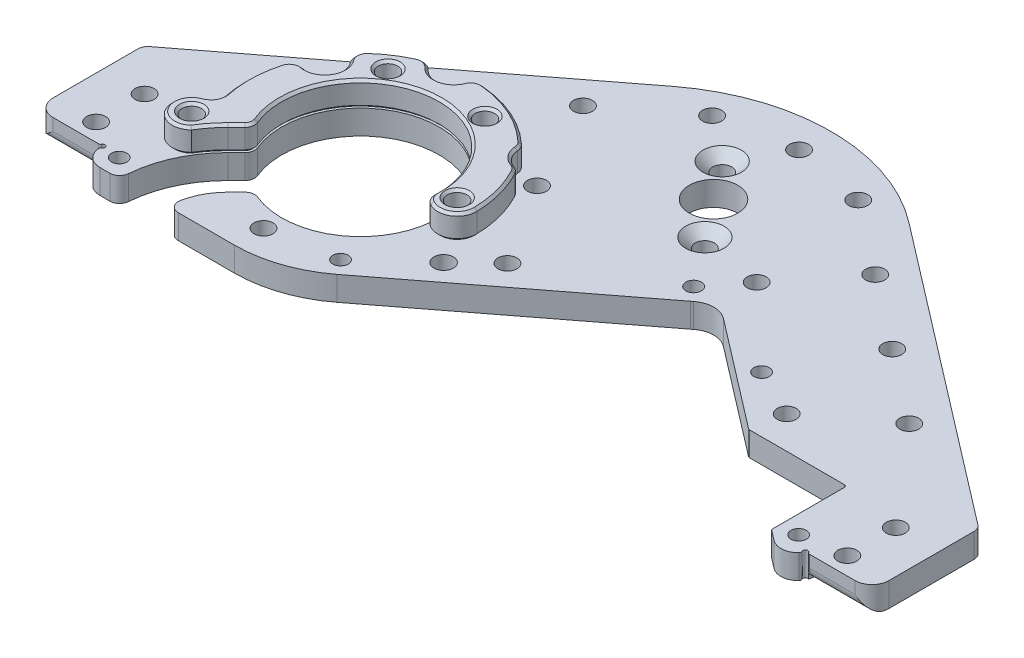
SolidWorks part; units mm, degrees
other "Weapon Motor Shock Spacer"
material "Alum Plate"
ref_plane "Front Plane" through (0, 0, 0) normal (0, 0, 1) x (1, 0, 0)
ref_plane "Top Plane" through (0, 0, 0) normal (0, 1, 0) x (1, 0, 0)
ref_plane "Right Plane" through (0, 0, 0) normal (1, 0, 0) x (0, 0, -1)
sketch "Top Layout" plane through (0, 0, 0) normal (0, 1, 0) x (1, 0, 0)
  line L0 (-114.046, -123.825) -> (-104.775, -123.825) construction
  line L1 (-104.775, -142.875) -> (-101.6, -142.875)
  line L2 (-104.775, -142.875) -> (-104.775, -104.775)
  line L3 (-104.775, -104.775) -> (-101.6, -104.775)
  line L4 (-101.6, -142.875) -> (-101.6, -104.775)
  line L5 (-104.775, -142.875) -> (-101.6, -104.775) construction
  line L6 (-104.775, -104.775) -> (-101.6, -142.875) construction
  line L7 (-19.05, -105.8164) -> (-101.6, -105.8164)
  line L8 (-19.05, -105.8164) -> (-19.05, -141.8336)
  line L9 (-19.05, -141.8336) -> (-101.6, -141.8336)
  line L10 (-101.6, -105.8164) -> (-101.6, -141.8336)
  line L11 (-19.05, -105.8164) -> (-101.6, -141.8336) construction
  line L12 (-19.05, -141.8336) -> (-101.6, -105.8164) construction
  line L13 (-133.096, -85.725) -> (-114.046, -85.725)
  line L14 (-133.096, -85.725) -> (-133.096, -161.925)
  line L15 (-133.096, -161.925) -> (-114.046, -161.925)
  line L16 (-114.046, -85.725) -> (-114.046, -161.925)
  line L17 (-133.096, -85.725) -> (-114.046, -161.925) construction
  line L18 (-133.096, -161.925) -> (-114.046, -85.725) construction
  line L19 (-104.775, -123.825) -> (0, -123.825) construction
  line L20 (0, -123.825) -> (0, 0) construction
  line L21 (-52.3528, -40.1717) -> (0, 0) construction
  line L22 (-70.6449, -16.3328) -> (-18.2922, 23.8388)
  line L23 (-34.0606, -64.0105) -> (18.2922, -23.8388)
  line L24 (-30.9251, 40.3023) -> (-122.2248, -29.7544)
  line L25 (-153.9748, -53.975) -> (-153.9748, -123.825)
  line L26 (-109.5248, -162.052) -> (109.5248, -162.052)
  line L27 (0, -162.052) -> (0, -123.825) construction
  line L28 (-109.5248, -162.052) -> (-109.5248, -20.0093) construction
  line L29 (-104.775, -142.875) -> (-104.775, -152.527)
  line L30 (-104.775, -152.527) -> (104.775, -152.527)
  line L31 (104.775, -104.775) -> (101.6, -104.775)
  line L32 (-144.4498, -73.025) -> (-109.5248, -73.025)
  line L33 (-144.4498, -73.025) -> (-144.4498, -123.825)
  line L34 (-144.4498, -123.825) -> (-109.5248, -123.825) construction
  line L35 (-109.5248, -73.025) -> (-109.5248, -162.052)
  line L36 (-144.4498, -73.025) -> (-109.5248, -123.825) construction
  line L37 (-144.4498, -123.825) -> (-109.5248, -73.025) construction
  line L38 (101.6, -142.875) -> (101.6, -104.775)
  line L39 (104.775, -142.875) -> (101.6, -142.875)
  line L40 (104.775, -142.875) -> (104.775, -104.775)
  line L41 (104.775, -142.875) -> (104.775, -152.527)
  line L42 (109.5248, -162.052) -> (109.5248, -20.0093) construction
  line L43 (30.9251, 40.3023) -> (122.2248, -29.7544)
  line L45 (19.05, -141.8336) -> (101.6, -141.8336)
  line L46 (101.6, -105.8164) -> (101.6, -141.8336)
  line L47 (19.05, -105.8164) -> (101.6, -105.8164)
  line L48 (19.05, -105.8164) -> (19.05, -141.8336)
  line L49 (133.096, -161.925) -> (114.046, -161.925)
  line L50 (114.046, -85.725) -> (114.046, -161.925)
  line L51 (133.096, -85.725) -> (114.046, -85.725)
  line L52 (133.096, -85.725) -> (133.096, -161.925)
  line L53 (144.4498, -123.825) -> (109.5248, -123.825) construction
  line L54 (109.5248, -73.025) -> (109.5248, -162.052)
  line L55 (144.4498, -73.025) -> (109.5248, -73.025)
  line L56 (144.4498, -73.025) -> (144.4498, -123.825)
  line L57 (-109.5248, -123.825) -> (-109.5248, -162.052) construction
  line L62 (-153.9748, -53.975) -> (-122.2248, -53.975)
  line L63 (-122.2248, -53.975) -> (-122.2248, -29.7544)
  line L64 (-144.4498, -123.825) -> (-153.9748, -123.825)
  line L65 (153.9748, -53.975) -> (153.9748, -123.825)
  line L66 (109.5248, -123.825) -> (109.5248, -162.052) construction
  line L67 (144.4498, -123.825) -> (153.9748, -123.825)
  line L68 (122.2248, -29.7544) -> (122.2248, -53.975)
  line L73 (-104.775, -104.775) -> (-104.775, -16.3647) construction
  line L74 (-95.25, -162.052) -> (-95.25, -9.0559) construction
  line L75 (-109.5248, -162.052) -> (-109.5248, -123.825) construction
  line L76 (109.5248, -162.052) -> (109.5248, -123.825) construction
  line L77 (122.2248, -53.975) -> (153.9748, -53.975)
  line L83 (104.775, -155.5496) -> (-104.775, -155.5496) construction
  line L88 (95.25, -162.052) -> (95.25, -9.0559) construction
  line L89 (104.775, -104.775) -> (104.775, -16.3647) construction
  line L92 (-104.775, -152.527) -> (-104.775, -162.052) construction
  line L93 (-14.605, -76.327) -> (14.605, -76.327)
  line L94 (-14.605, -76.327) -> (-14.605, -152.527)
  line L95 (-14.605, -152.527) -> (14.605, -152.527)
  line L96 (14.605, -76.327) -> (14.605, -152.527)
  line L97 (-14.605, -76.327) -> (14.605, -152.527) construction
  line L98 (-14.605, -152.527) -> (14.605, -76.327) construction
  line L99 (104.775, -152.527) -> (104.775, -162.052) construction
  line L100 (-19.05, -105.8164) -> (0, -105.8164) construction
  line L107 (0, -105.8164) -> (19.05, -105.8164) construction
  line L108 (104.775, -123.825) -> (114.046, -123.825) construction
  circle A0 centre (0, 0) radius 114.3
  circle A1 centre (0, 0) radius 6.35
  circle A2 centre (-52.3528, -40.1717) radius 17.8
  circle A3 centre (0, 0) radius 30.0482
  circle A4 centre (-52.3528, -40.1717) radius 30.0482
  arc A5 (-30.9251, 40.3023) -> (30.9251, 40.3023) centre (0, 0) cw
  point P2 (-103.1875, -123.825)
  point P7 (-60.325, -123.825)
  point P12 (-123.571, -123.825)
  point P30 (-126.9873, -98.425)
  point P35 (0, -114.427)
  point P53 (0, -152.527)
  dimension "D1" = 35.6
  dimension "D2" = 12.7
  dimension "D3" = 228.6
  dimension "D11" = 60.0964
  dimension "D12" = 50.8
  dimension "D14" = 52.5
  dimension "D4" = 3.175
  dimension "D5" = 19.05
  dimension "D6" = 76.2
  dimension "D7" = 82.55
  dimension "D8" = 38.1
  dimension "D9" = 104.775
  dimension "D10" = 18.0086
  dimension "D13" = 9.525
  dimension "D15" = 4.7498
  dimension "D16" = 9.525
  dimension "D17" = 9.652
  dimension "D18" = 50.8
  dimension "D19" = 12.446
  dimension "D20" = 65.9892
  dimension "D21" = 19.05
  dimension "D22" = 34.925
  dimension "D23" = 123.825
  dimension "D24" = 12.7
  dimension "D25" = 9.525
  dimension "D26" = 29.21
  dimension "D27" = 76.2
  dimension "D28" = 3.0226
sketch "Side Layout" plane through (0, 0, 0) normal (1, 0, 0) x (0, 0, -1)
  line L0 (0, -38.1) -> (0, 33.7344) construction
  line L1 (-114.3, -20.955) -> (114.3, -20.955)
  line L2 (-114.3, -20.955) -> (-114.3, -33.655)
  line L3 (-114.3, -33.655) -> (114.3, -33.655)
  line L4 (114.3, -20.955) -> (114.3, -33.655)
  line L5 (-114.3, -20.955) -> (114.3, -33.655) construction
  line L6 (-114.3, -33.655) -> (114.3, -20.955) construction
  line L7 (-9.525, -32.9406) -> (9.525, -32.9406)
  line L8 (-9.525, -32.9406) -> (-9.525, -38.1)
  line L9 (-9.525, -38.1) -> (9.525, -38.1)
  line L10 (9.525, -32.9406) -> (9.525, -38.1)
  line L11 (-9.525, -32.9406) -> (9.525, -38.1) construction
  line L12 (-9.525, -38.1) -> (9.525, -32.9406) construction
  line L13 (-11.9126, -29.3338) -> (11.9126, -29.3338)
  line L14 (-11.9126, -29.3338) -> (-11.9126, -32.9406)
  line L15 (-11.9126, -32.9406) -> (11.9126, -32.9406)
  line L16 (11.9126, -29.3338) -> (11.9126, -32.9406)
  line L17 (-11.9126, -29.3338) -> (11.9126, -32.9406) construction
  line L18 (-11.9126, -32.9406) -> (11.9126, -29.3338) construction
  line L19 (-6.35, -32.9406) -> (6.35, -32.9406)
  line L20 (-6.35, -32.9406) -> (-6.35, 33.7344)
  line L21 (-6.35, 33.7344) -> (6.35, 33.7344)
  line L22 (6.35, -32.9406) -> (6.35, 33.7344)
  line L23 (-6.35, -32.9406) -> (6.35, 33.7344) construction
  line L24 (-6.35, 33.7344) -> (6.35, -32.9406) construction
  line L25 (-162.052, 0) -> (-123.825, 0) construction
  line L26 (114.3, -33.655) -> (114.3, 0) construction
  line L27 (-142.875, 19.05) -> (-104.775, 19.05)
  line L28 (-40.1717, -9.525) -> (-40.1717, 5.4) construction
  line L29 (-142.875, 19.05) -> (-142.875, -19.05)
  line L30 (-142.875, -19.05) -> (-104.775, -19.05)
  line L31 (-104.775, 19.05) -> (-104.775, -19.05)
  line L32 (-142.875, 19.05) -> (-104.775, -19.05) construction
  line L33 (-142.875, -19.05) -> (-104.775, 19.05) construction
  line L34 (-130.175, -38.1) -> (-117.9516, -38.1) construction
  line L35 (-57.9717, -14.6) -> (-22.3717, -14.6)
  line L36 (-30.0482, -2.794) -> (30.0482, -2.794)
  line L37 (-30.0482, -2.794) -> (-30.0482, -20.955)
  line L38 (-30.0482, -20.955) -> (30.0482, -20.955)
  line L39 (30.0482, -2.794) -> (30.0482, -20.955)
  line L40 (-30.0482, -2.794) -> (30.0482, -20.955) construction
  line L41 (-30.0482, -20.955) -> (30.0482, -2.794) construction
  line L42 (-30.0482, -2.794) -> (-30.0482, 0) construction
  line L43 (-123.825, 0) -> (0, 0) construction
  line L44 (-57.9717, -14.6) -> (-57.9717, 25.4)
  line L45 (-57.9717, 25.4) -> (-22.3717, 25.4)
  line L46 (-22.3717, -14.6) -> (-22.3717, 25.4)
  line L47 (-19.05, 0) -> (19.05, 0)
  line L48 (-19.05, 0) -> (-19.05, -1.9812)
  line L49 (-19.05, -1.9812) -> (19.05, -1.9812)
  line L50 (19.05, 0) -> (19.05, -1.9812)
  line L51 (-19.05, 0) -> (19.05, -1.9812) construction
  line L52 (-19.05, -1.9812) -> (19.05, 0) construction
  line L53 (-70.2199, -3.175) -> (-10.1235, -3.175)
  line L54 (-70.2199, -3.175) -> (-70.2199, -15.875)
  line L55 (-70.2199, -15.875) -> (-10.1235, -15.875)
  line L56 (-10.1235, -3.175) -> (-10.1235, -15.875)
  line L57 (-70.2199, -3.175) -> (-10.1235, -15.875) construction
  line L58 (-70.2199, -15.875) -> (-10.1235, -3.175) construction
  line L59 (-40.1717, -9.525) -> (-40.1717, 0) construction
  line L60 (-57.9717, -14.6) -> (-22.3717, 25.4) construction
  line L61 (-57.9717, 25.4) -> (-22.3717, -14.6) construction
  line L62 (-22.3717, 0) -> (-57.9717, 0) construction
  line L63 (-137.8162, 0) -> (-123.825, -13.9912) construction
  line L64 (-139.065, 15.24) -> (-108.585, 15.24) construction
  line L65 (-139.065, 15.24) -> (-139.065, -15.24) construction
  line L66 (-139.065, -15.24) -> (-108.585, -15.24) construction
  line L67 (-108.585, 15.24) -> (-108.585, -15.24) construction
  line L68 (-139.065, 15.24) -> (-108.585, -15.24) construction
  line L69 (-139.065, -15.24) -> (-108.585, 15.24) construction
  line L70 (-137.8162, 0) -> (-123.825, 13.9912) construction
  line L71 (-123.825, -13.9912) -> (-109.8338, 0) construction
  line L72 (-123.825, 13.9912) -> (-109.8338, 0) construction
  line L73 (-137.8162, 0) -> (-109.8338, 0) construction
  line L74 (-123.825, -13.9912) -> (-123.825, 13.9912) construction
  line L75 (-6.35, 17.8594) -> (6.35, 17.8594)
  line L76 (114.3, 0) -> (-114.3, 0) construction
  line L77 (-22.3717, 19.05) -> (-6.35, 19.05) construction
  line L78 (-123.825, 38.1) -> (-97.9206, 38.1) construction
  line L79 (-19.05, -3.5814) -> (19.05, -3.5814)
  line L80 (-19.05, -3.5814) -> (-19.05, -1.9812)
  line L81 (-19.05, -1.9812) -> (19.05, -1.9812)
  line L82 (19.05, -3.5814) -> (19.05, -1.9812)
  line L83 (-19.05, -3.5814) -> (19.05, -1.9812) construction
  line L84 (-19.05, -1.9812) -> (19.05, -3.5814) construction
  line L85 (-8.7376, -16.7608) -> (8.7376, -16.7608)
  line L86 (-8.7376, -16.7608) -> (-8.7376, -29.3338)
  line L87 (-8.7376, -29.3338) -> (8.7376, -29.3338)
  line L88 (8.7376, -16.7608) -> (8.7376, -29.3338)
  line L89 (-8.7376, -16.7608) -> (8.7376, -29.3338) construction
  line L90 (-8.7376, -29.3338) -> (8.7376, -16.7608) construction
  line L91 (-8.7376, -3.5814) -> (8.7376, -3.5814)
  line L92 (-8.7376, -3.5814) -> (-8.7376, -16.1544)
  line L93 (-8.7376, -16.1544) -> (8.7376, -16.1544)
  line L94 (8.7376, -3.5814) -> (8.7376, -16.1544)
  line L95 (-8.7376, -3.5814) -> (8.7376, -16.1544) construction
  line L96 (-8.7376, -16.1544) -> (8.7376, -3.5814) construction
  circle A0 centre (-123.825, 0) radius 18.0086
  circle A1 centre (-123.825, 0) radius 38.1
  circle A2 centre (-139.065, 15.24) radius 1.905
  circle A3 centre (-108.585, 15.24) radius 1.905
  circle A4 centre (-108.585, -15.24) radius 1.905
  circle A5 centre (-139.065, -15.24) radius 1.905
  circle A6 centre (-137.8162, 0) radius 1.6002
  circle A7 centre (-123.825, 13.9912) radius 1.6002
  circle A8 centre (-109.8338, 0) radius 1.6002
  circle A9 centre (-123.825, -13.9912) radius 1.6002
  point P0 (0, -27.305)
  point P6 (0, -31.1372)
  point P7 (0, -35.5203)
  point P21 (0, 0.3969)
  point P32 (0, -11.8745)
  point P43 (0, -0.9906)
  point P55 (-40.1717, -9.525)
  point P72 (-40.1717, 5.4)
  point P88 (0, -23.0473)
  point P93 (0, -2.7813)
  point P102 (0, -9.8679)
  dimension "D17" = 3.81
  dimension "D18" = 3.2004
  dimension "D1" = 12.7
  dimension "D2" = 5.1594
  dimension "D3" = 19.05
  dimension "D4" = 3.6068
  dimension "D5" = 23.8252
  dimension "D6" = 12.7
  dimension "D7" = 18.161
  dimension "D8" = 1.9812
  dimension "D9" = 12.7
  dimension "D10" = 40
  dimension "D11" = 25.4
  dimension "D12" = 50.8
  dimension "D13" = 41.275
  dimension "D14" = 30.48
  dimension "D15" = 4.445
  dimension "D16" = 19.7866
  dimension "D19" = 15.875
  dimension "D20" = 6.35
  dimension "D21" = 38.1
  dimension "D22" = 1.6002
  dimension "D23" = 38.1
  dimension "D24" = 17.4752
  dimension "D25" = 12.573
ref_plane "Plane1" through (0, 25.4, 0) normal (0, 1, 0) x (1, 0, 0)
sketch "Sketch3" plane through (0, 25.4, 0) normal (0, 1, 0) x (1, 0, 0)
  line L0 (-104.775, -36.3747) -> (-30.9251, 20.2924)
  line L1 (-104.775, -104.775) -> (-104.775, -16.3647) construction
  line L2 (0, -200130.175) -> (0, 199882.0484) construction
  line L3 (-30.9251, 40.3023) -> (-122.2248, -29.7544) construction
  line L5 (-104.775, -36.3747) -> (-104.775, -77.6497)
  line L6 (-92.075, -77.6497) -> (-104.775, -77.6497)
  line L7 (30.9251, 20.2924) -> (104.775, -36.3747)
  line L8 (104.775, -77.6497) -> (92.075, -77.6497)
  line L9 (104.775, -36.3747) -> (104.775, -77.6497)
  line L11 (104.775, -104.775) -> (104.775, -16.3647) construction
  line L12 (30.9251, 40.3023) -> (122.2248, -29.7544) construction
  line L13 (92.075, -74.6536) -> (24.1423, -22.5271)
  line L14 (-32.2514, -66.3682) -> (20.1013, -26.1965)
  line L15 (-30.9251, 20.2924) -> (0, 44.022)
  line L16 (0, 44.022) -> (30.9251, 20.2924)
  line L17 (-92.075, -77.6497) -> (-92.075, -73.1917)
  line L19 (-92.075, -73.1917) -> (-52.3528, -73.1917)
  line L20 (92.075, -74.6536) -> (92.075, -77.6497)
  circle A1 centre (-52.3528, -40.1717) radius 20.6375
  circle A2 centre (0, 0) radius 6.35
  circle A3 centre (0, 0) radius 6.35 construction
  arc A4 (-52.3528, -73.1917) -> (-32.2514, -66.3682) centre (-52.3528, -40.1717) ccw
  arc A5 (20.1013, -26.1965) -> (24.1423, -22.5271) centre (0, 0) ccw
  arc A6 (30.9251, 20.2924) -> (-30.9251, 20.2924) centre (0, -20.01) ccw construction
  point P28 (0, 44.022)
  dimension "D1" = 33.02
  dimension "D5" = 50.8
  dimension "D7" = 41.275
  dimension "D2" = 41.275
  dimension "D3" = 34.925
  dimension "D4" = 12.7
  dimension "D6" = 38.1
extrude "Boss-Extrude1" add sketch "Sketch3" against normal blind 6.35
ref_plane "Plane3" through (-104.775, 0, 0) normal (-1, 0, 0) x (0, 0, 1)
sketch "Sketch6" plane through (-104.775, 0, 0) normal (-1, 0, 0) x (0, 0, 1)
  line L0 (162.052, -25.4) -> (162.052, 25.4)
  line L1 (162.052, 25.4) -> (77.6497, 25.4)
  line L2 (36.3747, 25.4) -> (77.6497, 25.4) construction
  line L3 (147.7645, 11.1125) -> (162.052, 11.1125) construction
  line L4 (162.052, 0) -> (71.2997, 0) construction
  line L5 (77.6497, 25.4) -> (77.6497, 19.05)
  line L6 (77.6497, 19.05) -> (36.3747, 19.05)
  line L7 (36.3747, 19.05) -> (36.3747, 6.35)
  line L8 (36.3747, 6.35) -> (71.2997, 6.35)
  line L10 (99.6315, -3.175) -> (99.6315, 11.1125) construction
  line L11 (71.2997, -25.4) -> (162.052, -25.4)
  line L13 (71.2997, 6.35) -> (71.2997, -25.4)
  line L14 (152.527, -25.4) -> (152.527, 25.4) construction
  line L15 (99.6315, 11.1125) -> (99.6315, 25.4) construction
  line L16 (147.7645, 11.1125) -> (147.7645, 25.4) construction
  line L17 (94.869, -7.9375) -> (104.394, -7.9375) construction
  line L18 (94.869, -7.9375) -> (94.869, 25.4) construction
  line L19 (94.869, 25.4) -> (104.394, 25.4) construction
  line L20 (104.394, -7.9375) -> (104.394, 25.4) construction
  line L21 (94.869, -7.9375) -> (104.394, 25.4) construction
  line L22 (94.869, 25.4) -> (104.394, -7.9375) construction
  line L23 (147.7645, 11.1125) -> (147.7645, -3.175) construction
  line L24 (104.394, -7.9375) -> (123.825, -7.9375) construction
  line L25 (143.002, -7.9375) -> (152.527, -7.9375) construction
  line L26 (143.002, -7.9375) -> (143.002, 25.4) construction
  line L27 (143.002, 25.4) -> (152.527, 25.4) construction
  line L28 (152.527, -7.9375) -> (152.527, 25.4) construction
  line L29 (143.002, -7.9375) -> (152.527, 25.4) construction
  line L30 (143.002, 25.4) -> (152.527, -7.9375) construction
  line L31 (123.825, -7.9375) -> (152.527, -7.9375) construction
  line L32 (104.775, 19.05) -> (104.775, -19.05) construction
  line L34 (155.702, -25.4) -> (155.702, 25.4) construction
  circle A0 centre (109.8338, 0) radius 1.6002 construction
  circle A1 centre (123.825, 13.9912) radius 1.6002 construction
  circle A2 centre (137.8162, 0) radius 1.6002 construction
  circle A3 centre (123.825, -13.9912) radius 1.6002 construction
  circle A4 centre (109.8338, 0) radius 1.6002 construction
  circle A5 centre (123.825, 13.9912) radius 1.6002 construction
  circle A6 centre (137.8162, 0) radius 1.6002 construction
  circle A7 centre (123.825, -13.9912) radius 1.6002 construction
  circle A8 centre (123.825, 0) radius 18.0086 construction
  circle A9 centre (123.825, 0) radius 18.0086 construction
  circle A10 centre (123.825, 0) radius 9.525
  circle A11 centre (108.585, -15.24) radius 1.905 construction
  circle A12 centre (108.585, 15.24) radius 1.905 construction
  circle A13 centre (139.065, 15.24) radius 1.905 construction
  circle A14 centre (139.065, -15.24) radius 1.905 construction
  circle A15 centre (108.585, -15.24) radius 1.905
  circle A16 centre (108.585, 15.24) radius 1.905
  circle A17 centre (139.065, 15.24) radius 1.905
  circle A18 centre (139.065, -15.24) radius 1.905
  circle A19 centre (147.7645, 11.1125) radius 2.5527
  circle A26 centre (99.6315, 11.1125) radius 2.5527
  circle A27 centre (99.6315, -3.175) radius 2.5527
  circle A28 centre (147.7645, -3.175) radius 2.5527
  point P29 (0, 0)
  point P55 (99.6315, 8.7312)
  point P61 (147.7645, 8.7312)
  dimension "D4" = 19.05
  dimension "D7" = 5.1054
  dimension "D1" = 6.35
  dimension "D2" = 12.7
  dimension "D3" = 25.4
  dimension "D5" = 6.35
  dimension "D6" = 3.175
  dimension "D8" = 0.381
  dimension "D9" = 14.2875
  dimension "D10" = 9.525
  dimension "D12" = 33.3375
sketch "Sketch12" [suppressed] plane through (0, 19.05, 0) normal (0, 1, 0) x (1, 0, 0)
  line L0 (-104.775, -77.6497) -> (-104.775, -36.3747)
  line L1 (-104.775, -36.3747) -> (-92.075, -36.3747)
  line L3 (-92.075, -36.3747) -> (-92.075, -77.6497)
  line L5 (-92.075, -77.6497) -> (-104.775, -77.6497)
  line L6 (-98.425, -77.6497) -> (-98.425, -63.3622) construction
  line L7 (-98.425, -63.3622) -> (-98.425, -50.6622) construction
  line L8 (-98.425, -50.6622) -> (-98.425, -36.3747) construction
  line L10 (-98.425, -36.3747) -> (-104.775, -36.3747) construction
  circle A0 centre (-98.425, -63.3622) radius 2.5527
  circle A1 centre (-98.425, -50.6622) radius 2.5527
  dimension "D2" = 5.1054
  dimension "D1" = 12.7
  dimension "D3" = 12.7
sketch "Sketch8" plane through (0, 25.4, 0) normal (0, 1, 0) x (1, 0, 0)
  line L0 (-109.5248, -162.052) -> (-109.5248, -20.0093) construction
  line L1 (-104.775, -77.6497) -> (-109.5248, -77.6497)
  line L2 (-104.775, -77.6497) -> (-104.775, -36.3747)
  line L3 (-104.775, -36.3747) -> (-109.5248, -36.3747)
  line L4 (-109.5248, -77.6497) -> (-109.5248, -36.3747)
  line L5 (-104.775, -77.6497) -> (-109.5248, -36.3747) construction
  line L6 (-104.775, -36.3747) -> (-109.5248, -77.6497) construction
  line L7 (104.775, -77.6497) -> (109.5248, -77.6497)
  line L8 (104.775, -77.6497) -> (104.775, -36.3747)
  line L9 (104.775, -36.3747) -> (109.5248, -36.3747)
  line L10 (109.5248, -77.6497) -> (109.5248, -36.3747)
  line L11 (104.775, -77.6497) -> (109.5248, -36.3747) construction
  line L12 (104.775, -36.3747) -> (109.5248, -77.6497) construction
  point P4 (-107.1499, -57.0122)
  point P10 (107.1499, -57.0122)
extrude "Boss-Extrude4" add sketch "Sketch8" against normal through all
sketch "Sketch9" plane through (0, 25.4, 0) normal (0, 1, 0) x (1, 0, 0)
  line L0 (7.4916, -9.7632) -> (0, 0) construction
  line L1 (0, 0) -> (-7.4916, 9.7632) construction
  line L2 (0, 44.022) -> (-104.775, -36.3747) construction
  circle A0 centre (-7.4916, 9.7632) radius 2.4892
  circle A1 centre (7.4916, -9.7632) radius 2.4892
  dimension "D2" = 4.9784
  dimension "D1" = 24.6126
extrude "Collar Holes" cut sketch "Sketch9" against normal through all
sketch "Sketch10" plane through (0, 25.4, 0) normal (0, 1, 0) x (1, 0, 0)
  line L0 (0, 33.4567) -> (0, 30.79) construction
  line L1 (-5.1026, 40.1066) -> (0, 33.4567) construction
  line L2 (0, 33.4567) -> (5.1026, 40.1066) construction
  line L3 (0, 44.022) -> (-104.775, -36.3747) construction
  line L4 (104.775, -36.3747) -> (0, 44.022) construction
  circle A0 centre (0, 33.4567) radius 4.7625 construction
  circle A1 centre (0, 33.4567) radius 2.0193
  arc A3 (30.9251, 20.2924) -> (-30.9251, 20.2924) centre (0, -20.01) ccw construction
  dimension "D2" = 9.525
  dimension "D3" = 4.0386
  dimension "D1" = 8.382
extrude "Spacer Holes" cut sketch "Sketch10" against normal through all
pattern_linear "Spacer Hole Pattern" count 5 spacing 24.13 along (-0.7934, 0, 0.6088) of "Spacer Holes"
mirror "Spacer Hole Mirror" about plane through (0, 0, 0) normal (1, 0, 0) of "Spacer Hole Pattern"
sketch "Sketch16" plane through (0, 25.4, 0) normal (0, 1, 0) x (1, 0, 0)
  line L0 (-109.5248, -50.6622) -> (-98.425, -50.6622) construction
  line L1 (-109.5248, -36.3747) -> (-109.5248, -77.6497) construction
  line L2 (-98.425, -50.6622) -> (-98.425, -63.3622) construction
  line L3 (-98.425, -63.3622) -> (-109.5248, -63.3622) construction
  line L4 (-98.425, -63.3622) -> (-98.425, -77.6497) construction
  line L5 (-109.5248, -77.6497) -> (-92.075, -77.6497) construction
  line L6 (-98.425, -50.6622) -> (-98.425, -36.3747) construction
  line L7 (-104.775, -36.3747) -> (-109.5248, -36.3747) construction
  line L8 (-104.775, -36.3747) -> (-104.775, -77.6497) construction
  line L9 (0, 0) -> (0, 30.79) construction
  line L10 (104.775, -36.3747) -> (104.775, -77.6497) construction
  circle A0 centre (-98.425, -50.6622) radius 2.0193
  circle A1 centre (-98.425, -63.3622) radius 2.0193
  circle A4 centre (98.425, -63.3622) radius 2.0193
  circle A5 centre (98.425, -50.6622) radius 2.0193
  arc A6 (30.9251, 20.2924) -> (-30.9251, 20.2924) centre (0, -20.01) ccw construction
  dimension "D1" = 4.0386
  dimension "D2" = 12.7
  dimension "D3" = 6.35
extrude "Custom Nutstrip Holes" cut sketch "Sketch16" against normal through all
sketch "Sketch36" plane through (0, 25.4, 0) normal (0, 1, 0) x (1, 0, 0)
  line L0 (-52.3528, -65.5717) -> (-12.44, -41.5615) construction
  line L1 (-12.44, -41.5615) -> (24.5129, -13.2066) construction
  line L2 (24.5129, -13.2066) -> (58.2939, -39.1277) construction
  line L3 (-32.2514, -66.3682) -> (20.1013, -26.1965) construction
  line L4 (24.1423, -22.5271) -> (92.075, -74.6536) construction
  line L5 (-12.44, -41.5615) -> (-7.8012, -47.6069) construction
  line L6 (58.2939, -39.1277) -> (53.6552, -45.1731) construction
  line L7 (-52.3528, -65.5717) -> (-52.3528, -40.1717) construction
  line L8 (58.2939, -39.1277) -> (92.075, -65.0488) construction
  line L9 (92.075, -65.0488) -> (92.075, -77.6497) construction
  line L10 (-52.3528, -40.1717) -> (-26.1764, -20.0858) construction
  line L11 (-26.1764, -20.0858) -> (0, 0) construction
  line L12 (92.075, -74.6536) -> (92.075, -77.6497) construction
  circle A0 centre (-52.3528, -65.5717) radius 2.0193
  circle A1 centre (58.2939, -39.1277) radius 2.0193
  circle A2 centre (24.5129, -13.2066) radius 2.0193
  circle A3 centre (-12.44, -41.5615) radius 2.0193
  circle A4 centre (-76.5745, -25.3009) radius 2.0193 construction
  circle A5 centre (-52.3528, -65.5717) radius 4.7625 construction
  circle A6 centre (-12.44, -41.5615) radius 4.7625 construction
  circle A7 centre (24.5129, -13.2066) radius 4.7625 construction
  circle A8 centre (58.2939, -39.1277) radius 4.7625 construction
  arc A9 (-52.3528, -73.1917) -> (-32.2514, -66.3682) centre (-52.3528, -40.1717) ccw construction
  circle A10 centre (-26.1764, -20.0858) radius 2.0193
  dimension "D1" = 9.525
  dimension "D2" = 25.4
  dimension "D3" = 7.62
extrude "Aux Spacer Holes" cut sketch "Sketch36" against normal through all
sketch "Sketch38" [suppressed] plane through (-104.775, 0, 0) normal (-1, 0, 0) x (0, 0, 1)
  line L1 (152.527, -7.9375) -> (143.002, -7.9375)
  line L2 (152.527, -7.9375) -> (152.527, 25.4)
  line L3 (152.527, 25.4) -> (143.002, 25.4)
  line L4 (143.002, -7.9375) -> (143.002, 25.4)
  line L5 (152.527, -7.9375) -> (143.002, 25.4) construction
  line L6 (152.527, 25.4) -> (143.002, -7.9375) construction
  point P4 (147.7645, 8.7312)
extrude "Cut-Extrude16" [suppressed] cut sketch "Sketch38" against normal blind 9.525
sketch "Sketch46" [suppressed] plane through (-104.775, 0, 0) normal (-1, 0, 0) x (0, 0, 1)
  line L0 (142.875, 19.05) -> (104.775, -19.05) construction
  line L1 (104.14, 19.685) -> (143.51, 19.685)
  line L2 (104.14, 19.685) -> (104.14, -19.685)
  line L3 (104.14, -19.685) -> (143.51, -19.685)
  line L4 (143.51, 19.685) -> (143.51, -19.685)
  line L5 (104.14, 19.685) -> (143.51, -19.685) construction
  line L6 (104.14, -19.685) -> (143.51, 19.685) construction
  point P0 (123.825, 0)
  dimension "D1" = 39.37
extrude "Cut-Extrude21" [suppressed] cut sketch "Sketch46" against normal blind 6.985
ref_plane "Plane5" through (0, 0, 152.527) normal (0, 0, 1) x (1, 0, 0)
sketch "Sketch41" plane through (0, 0, 152.527) normal (0, 0, 1) x (1, 0, 0)
  line L0 (-104.775, -7.9375) -> (-104.775, 25.4) construction
  line L1 (-104.775, -7.9375) -> (-104.775, 12.7)
  line L2 (-104.775, -7.9375) -> (104.775, -7.9375)
  line L3 (104.775, -7.9375) -> (104.775, 12.7)
  line L4 (104.775, 25.4) -> (-104.775, 25.4)
  line L5 (0, -7.9375) -> (0, 25.4) construction
  line L6 (-104.775, 3.9624) -> (-100.0125, 3.9624) construction
  line L7 (-100.0125, 3.9624) -> (-100.0125, 25.4) construction
  line L8 (104.775, 3.9624) -> (100.0125, 3.9624) construction
  line L9 (100.0125, 3.9624) -> (100.0125, 25.4) construction
  line L10 (19.05, 20.6375) -> (23.8252, 20.6375) construction
  line L11 (19.05, 15.875) -> (78.5876, 15.875) construction
  line L12 (19.05, 15.875) -> (19.05, 25.4) construction
  line L13 (19.05, 25.4) -> (78.5876, 25.4) construction
  line L14 (78.5876, 15.875) -> (78.5876, 25.4) construction
  line L15 (19.05, 15.875) -> (78.5876, 25.4) construction
  line L16 (19.05, 25.4) -> (78.5876, 15.875) construction
  line L17 (23.8252, 20.6375) -> (38.1127, 20.6375) construction
  line L18 (38.1127, 20.6375) -> (52.4002, 20.6375) construction
  line L19 (52.4002, 20.6375) -> (66.6877, 20.6375) construction
  line L20 (-104.775, 25.4) -> (-112.395, 25.4)
  line L21 (-112.395, 25.4) -> (-112.395, 3.175)
  line L22 (-112.395, 3.175) -> (-109.5248, 3.175)
  line L23 (-109.5248, 3.175) -> (-109.5248, 12.7)
  line L24 (-109.5248, 12.7) -> (-104.775, 12.7)
  line L25 (-104.775, 12.7) -> (-104.775, 25.4) construction
  line L26 (104.775, 25.4) -> (112.395, 25.4)
  line L27 (112.395, 25.4) -> (112.395, 3.175)
  line L28 (112.395, 3.175) -> (109.5248, 3.175)
  line L29 (109.5248, 3.175) -> (109.5248, 12.7)
  line L30 (109.5248, 12.7) -> (104.775, 12.7)
  line L31 (104.775, 12.7) -> (104.775, 25.4) construction
  line L32 (-100.0125, 3.9624) -> (-87.3125, 3.9624) construction
  line L33 (-63.5, -1.5875) -> (0, -1.5875) construction
  line L34 (0, -1.5875) -> (63.5, -1.5875) construction
  line L35 (63.5, -1.5875) -> (63.5, -7.9375) construction
  circle A0 centre (-100.0125, 3.9624) radius 2.5527
  circle A1 centre (100.0125, 3.9624) radius 2.5527
  circle A2 centre (23.8252, 20.6375) radius 2.5527
  circle A3 centre (38.1127, 20.6375) radius 2.5527
  circle A4 centre (52.4002, 20.6375) radius 2.5527
  circle A5 centre (66.6877, 20.6375) radius 2.5527
  circle A6 centre (-66.6877, 20.6375) radius 2.5527
  circle A7 centre (-52.4002, 20.6375) radius 2.5527
  circle A8 centre (-38.1127, 20.6375) radius 2.5527
  circle A9 centre (-23.8252, 20.6375) radius 2.5527
  circle A10 centre (-87.3125, 3.9624) radius 2.5527
  circle A11 centre (87.3125, 3.9624) radius 2.5527
  circle A12 centre (-63.5, -1.5875) radius 2.5527
  circle A13 centre (63.5, -1.5875) radius 2.5527
  point P14 (48.8188, 20.6375)
  dimension "D3" = 5.1054
  dimension "D7" = 5.1054
  dimension "D1" = 21.4376
  dimension "D2" = 4.7625
  dimension "D4" = 9.525
  dimension "D5" = 59.5376
  dimension "D6" = 4.7752
  dimension "D8" = 14.2875
  dimension "D9" = 7.62
  dimension "D10" = 4.7498
  dimension "D11" = 12.7
  dimension "D12" = 9.525
  dimension "D13" = 19.05
  dimension "D14" = 12.7
  dimension "D15" = 6.35
  dimension "D16" = 63.5
sketch "Sketch43" [suppressed] plane through (-109.5248, 0, 0) normal (-1, 0, 0) x (0, 0, 1)
  line L1 (152.527, 12.7) -> (155.702, 12.7)
  line L2 (152.527, 12.7) -> (152.527, 25.4)
  line L3 (152.527, 25.4) -> (155.702, 25.4)
  line L4 (155.702, 12.7) -> (155.702, 25.4)
  line L5 (152.527, 12.7) -> (155.702, 25.4) construction
  line L6 (152.527, 25.4) -> (155.702, 12.7) construction
  line L7 (162.052, 25.4) -> (77.6497, 25.4) construction
  point P4 (154.1145, 19.05)
  dimension "D1" = 3.175
sketch "Sketch44" plane through (0, 25.4, 0) normal (0, 1, 0) x (1, 0, 0)
  line L0 (73.8315, -147.7645) -> (73.8315, -152.527) construction
  line L1 (92.075, -74.6536) -> (92.075, -77.6497) construction
  line L2 (-92.075, -77.6497) -> (-92.075, -73.1917) construction
  line L3 (0, -123.825) -> (0, 0) construction
  line L4 (-92.075, -73.1917) -> (-52.3528, -73.1917) construction
  line L5 (-104.775, -104.775) -> (-104.775, -16.3647) construction
  line L6 (-32.2514, -66.3682) -> (20.1013, -26.1965) construction
  line L21 (-104.775, -68.1247) -> (-104.775, -152.527)
  line L22 (-104.775, -152.527) -> (104.775, -152.527)
  line L23 (104.775, -152.527) -> (104.775, -68.1247)
  line L34 (-104.775, -99.6315) -> (-100.0125, -99.6315) construction
  line L35 (-104.775, -147.7645) -> (-100.0125, -147.7645) construction
  line L36 (0, -152.527) -> (0, -35.6178) construction
  line L38 (30.969, -147.7645) -> (45.2565, -147.7645) construction
  line L39 (45.2565, -147.7645) -> (59.544, -147.7645) construction
  line L40 (59.544, -147.7645) -> (73.8315, -147.7645) construction
  line L41 (23.8252, -152.527) -> (30.969, -152.527) construction
  line L42 (104.775, -152.527) -> (-104.775, -152.527) construction
  line L43 (30.969, -152.527) -> (38.1127, -152.527) construction
  line L44 (30.969, -152.527) -> (30.969, -147.7645) construction
  line L45 (-92.075, -77.6497) -> (-104.775, -77.6497) construction
  line L48 (-35.1507, -62.5899) -> (-8.9743, -42.504) construction
  line L49 (-8.9743, -42.504) -> (17.2021, -22.4182) construction
  line L50 (45.5313, -32.9364) -> (87.3125, -64.9962) construction
  line L51 (92.075, -74.6536) -> (24.1423, -22.5271) construction
  line L52 (104.775, -77.6497) -> (92.075, -77.6497) construction
  line L79 (-104.775, -68.1247) -> (-92.075, -68.1247)
  line L80 (-92.075, -68.1247) -> (-92.075, -63.6667)
  line L85 (21.8118, -8.7328) -> (92.075, -62.6476)
  line L86 (-38.0499, -58.8115) -> (14.3028, -18.6398)
  line L87 (-92.075, -63.6667) -> (-52.3528, -63.6667)
  line L88 (92.075, -62.6476) -> (92.075, -68.1247)
  line L89 (92.075, -68.1247) -> (104.775, -68.1247)
  circle A0 centre (-73.8315, -147.7645) radius 2.5527
  circle A1 centre (-59.544, -147.7645) radius 2.5527
  circle A2 centre (-45.2565, -147.7645) radius 2.5527
  circle A3 centre (-30.969, -147.7645) radius 2.5527
  circle A17 centre (-100.0125, -99.6315) radius 2.5527
  circle A18 centre (-100.0125, -147.7645) radius 2.5527
  circle A19 centre (100.0125, -147.7645) radius 2.5527
  circle A20 centre (100.0125, -99.6315) radius 2.5527
  circle A21 centre (30.969, -147.7645) radius 2.5527
  circle A22 centre (45.2565, -147.7645) radius 2.5527
  circle A23 centre (59.544, -147.7645) radius 2.5527
  circle A24 centre (73.8315, -147.7645) radius 2.5527
  circle A25 centre (-87.3125, -68.4292) radius 4.7625 construction
  circle A26 centre (-35.1507, -62.5899) radius 4.7625 construction
  circle A27 centre (-8.9743, -42.504) radius 4.7625 construction
  circle A28 centre (17.2021, -22.4182) radius 4.7625 construction
  circle A29 centre (45.5313, -32.9364) radius 4.7625 construction
  circle A30 centre (87.3125, -64.9962) radius 4.7625 construction
  circle A32 centre (-87.3125, -68.4292) radius 2.5527
  circle A33 centre (-35.1507, -62.5899) radius 2.5527
  circle A34 centre (-8.9743, -42.504) radius 2.5527 construction
  circle A35 centre (17.2021, -22.4182) radius 2.5527
  circle A36 centre (45.5313, -32.9364) radius 2.5527
  circle A37 centre (87.3125, -64.9962) radius 2.5527
  circle A38 centre (-97.155, -85.2697) radius 7.62 construction
  circle A39 centre (97.155, -85.2697) radius 7.62 construction
  circle A40 centre (24.5121, -32.4156) radius 7.62 construction
  arc A41 (20.1013, -26.1965) -> (24.1423, -22.5271) centre (0, 0) ccw construction
  circle A42 centre (-97.155, -85.2697) radius 2.5527
  circle A43 centre (24.5121, -32.4156) radius 2.5527
  circle A44 centre (97.155, -85.2697) radius 2.5527
  arc A56 (14.3028, -18.6398) -> (21.8118, -8.7328) centre (0, 0) ccw
  arc A57 (-52.3528, -63.6667) -> (-38.0499, -58.8115) centre (-52.3528, -40.1717) ccw
  point P4 (-104.775, -152.527)
  dimension "D2" = 5.1054
  dimension "D7" = 5.1054
  dimension "D8" = 15.24
  dimension "D3" = 9.525
  dimension "D9" = 9.525
  dimension "D4" = 4.7625
  dimension "D5" = 14.2875
  dimension "D6" = 9.525
  dimension "D1" = 4.7625
  dimension "D10" = 52.664
sketch "Sketch82" [suppressed] plane through (0, 28.829, 0) normal (0, 1, 0) x (1, 0, 0)
  line L0 (-52.3528, -63.6667) -> (-92.075, -63.6667) construction
  line L1 (-52.3528, -65.5717) -> (-52.3528, -63.6667) construction
  line L2 (-12.4467, -41.5667) -> (-13.6064, -40.0553) construction
  line L3 (14.3028, -18.6398) -> (-38.0499, -58.8115) construction
  line L4 (24.5175, -13.2101) -> (25.6772, -11.6988) construction
  line L5 (92.075, -62.6476) -> (21.8118, -8.7328) construction
  line L6 (58.2962, -39.1295) -> (59.4559, -37.6181) construction
  line L7 (21.4643, -9.5551) -> (21.8118, -8.7328)
  line L8 (21.8118, -8.7328) -> (22.2143, -9.0416)
  circle A0 centre (-52.3528, -65.5717) radius 4.7625
  circle A1 centre (-12.4467, -41.5667) radius 4.7625
  arc A2 (21.4643, -9.5551) -> (22.2143, -9.0416) centre (24.5175, -13.2101) ccw
  circle A3 centre (58.2962, -39.1295) radius 4.7625
  arc A4 (14.3028, -18.6398) -> (21.8118, -8.7328) centre (0, 0) ccw construction
  dimension "D1" = 9.525
  dimension "D2" = 1.905
  dimension "D3" = 30.8104
  dimension "D4" = 83.6926
  dimension "D5" = 41.1154
extrude "Cut-Extrude38" [suppressed] cut sketch "Sketch82" against normal up to surface (3.429 mm away)
sketch "Sketch45" [suppressed] plane through (0, -25.4, 0) normal (0, -1, 0) x (1, 0, 0)
  circle A2 centre (24.5121, 32.4156) radius 6.35
  circle A4 centre (-97.155, 85.2697) radius 6.35
  circle A5 centre (97.155, 85.2697) radius 6.35
  dimension "D1" = 12.7
ref_plane "Plane6" through (0, 19.05, 0) normal (0, 1, 0) x (1, 0, 0)
sketch "Sketch59" [suppressed] plane through (0, 19.05, 0) normal (0, 1, 0) x (1, 0, 0)
  line L0 (0, 22.408) -> (0, 30.79) construction
  line L1 (-19.1436, 18.7673) -> (-24.2463, 25.4172) construction
  line L2 (0, 33.4567) -> (-5.1026, 40.1066) construction
  line L3 (-5.1026, 40.1066) -> (-24.2463, 25.4172) construction
  line L4 (-104.775, -36.3747) -> (-30.9251, 20.2924) construction
  line L5 (-19.1436, 18.7673) -> (0, 33.4567) construction
  circle A0 centre (0, 22.408) radius 4.7625
  circle A2 centre (-19.1436, 18.7673) radius 4.7625
  arc A3 (30.9251, 20.2924) -> (-30.9251, 20.2924) centre (0, -20.01) ccw construction
  dimension "D3" = 9.525
  dimension "D1" = 8.382
  dimension "D2" = 24.13
sketch "Sketch47" plane through (0, 25.4, 0) normal (0, 1, 0) x (1, 0, 0)
  line L0 (-21.3485, -42.7945) -> (-23.7291, -44.6212) construction
  line L1 (-81.9672, -61.1267) -> (-75.3534, -61.1267) construction
  line L2 (-19.1436, 18.7673) -> (-38.2872, 4.0779) construction
  line L3 (-38.2872, 4.0779) -> (-57.4308, -10.6115) construction
  line L4 (-57.4308, -10.6115) -> (-76.5745, -25.3009) construction
  line L5 (-19.1436, 18.7673) -> (0, 33.4567) construction
  line L6 (-76.5745, -25.3009) -> (-65.8758, -19.4248) construction
  line L7 (-65.8758, -19.4248) -> (-57.4308, -10.6115) construction
  line L9 (-87.7466, -52.146) -> (-71.6552, -16.7941)
  line L10 (-38.0499, -58.8115) -> (14.3028, -18.6398) construction
  line L11 (-81.9672, -54.7767) -> (-52.3528, -40.1717) construction
  line L12 (-52.3528, -40.1717) -> (-65.8758, -19.4248) construction
  line L13 (-92.075, -63.6667) -> (-52.3528, -63.6667) construction
  line L14 (-70.5066, -49.3452) -> (-83.977, -62.8156) construction
  line L15 (-23.7291, -44.6212) -> (-39.5962, -56.7964)
  line L16 (-52.3528, -61.1267) -> (-81.9672, -61.1267)
  line L17 (-42.4227, -17.4847) -> (-52.3528, -40.1717) construction
  line L18 (-52.3528, -40.1717) -> (-27.5947, -39.5834) construction
  line L19 (-81.9672, -54.7767) -> (-65.8758, -19.4248) construction
  line L20 (-65.8758, -19.4248) -> (-42.4227, -17.4847) construction
  line L21 (-42.4227, -17.4847) -> (-27.5947, -39.5834) construction
  line L22 (-83.977, -62.8156) -> (-74.9967, -71.7959) construction
  line L23 (-74.9967, -71.7959) -> (-61.5263, -58.3255) construction
  line L24 (-79.4868, -67.3058) -> (-52.3528, -40.1717) construction
  line L25 (-52.3528, -60.5117) -> (-52.3528, -40.1717) construction
  arc A0 (-87.7466, -52.146) -> (-81.9672, -61.1267) centre (-81.9672, -54.7767) ccw
  arc A1 (-23.7291, -44.6212) -> (-27.4458, -33.2351) centre (-27.5947, -39.5834) ccw
  arc A2 (-60.2505, -16.4788) -> (-71.6552, -16.7941) centre (-65.8758, -19.4248) ccw
  arc A3 (-36.4919, -19.7535) -> (-48.4556, -15.5031) centre (-42.4227, -17.4847) ccw
  arc A4 (-21.3485, -42.7945) -> (-75.3534, -61.1267) centre (-52.3528, -40.1717) ccw construction
  arc A5 (-52.3528, -63.6667) -> (-38.0499, -58.8115) centre (-52.3528, -40.1717) ccw construction
  arc A6 (-52.3528, -61.1267) -> (-39.5962, -56.7964) centre (-52.3528, -40.1717) ccw
  circle A7 centre (-81.9672, -54.7767) radius 2.4892
  circle A8 centre (-65.8758, -19.4248) radius 2.4892
  circle A9 centre (-42.4227, -17.4847) radius 2.4892
  circle A10 centre (-27.5947, -39.5834) radius 2.4892
  circle A11 centre (-52.3528, -40.1717) radius 6.985
  arc A13 (-60.2505, -16.4788) -> (-48.4556, -15.5031) centre (-54.5593, -13.4984) ccw
  arc A14 (-36.4919, -19.7535) -> (-27.4458, -33.2351) centre (-27.2129, -23.3031) ccw
  circle A15 centre (-52.3528, -40.1717) radius 20.34 construction
  circle A16 centre (-52.3528, -40.1717) radius 17.8 construction
  dimension "D2" = 62.23
  dimension "D3" = 4.9784
  dimension "D7" = 13.97
  dimension "D8" = 45
  dimension "D10" = 12.7
  dimension "D11" = 2.54
  dimension "D4" = 2.54
  dimension "D5" = 33.02
  dimension "D6" = 6.35
  dimension "D9" = 65
  dimension "D12" = 19.05
sketch "Sketch49" plane through (0, 25.4, 0) normal (0, 1, 0) x (1, 0, 0)
  circle A0 centre (-81.9672, -54.7767) radius 2.0193
  circle A1 centre (-65.8758, -19.4248) radius 2.0193
  circle A2 centre (-42.4227, -17.4847) radius 2.0193
  circle A3 centre (-27.5947, -39.5834) radius 2.0193
  dimension "D1" = 4.0386
extrude "Cut-Extrude23" cut sketch "Sketch49" against normal through all
sketch "Sketch50" plane through (0, 25.4, 0) normal (0, 1, 0) x (1, 0, 0)
  circle A0 centre (-87.3125, -68.4292) radius 2.0193
  circle A1 centre (-35.1507, -62.5899) radius 2.0193
  circle A3 centre (17.2021, -22.4182) radius 2.0193
  circle A4 centre (45.5313, -32.9364) radius 2.0193
  circle A5 centre (87.3125, -64.9962) radius 2.0193
  circle A6 centre (-27.5947, -39.5834) radius 2.0193 construction
extrude "Cut-Extrude24" cut sketch "Sketch50" against normal through all
sketch "Sketch58" plane through (0, 25.4, 0) normal (0, 1, 0) x (1, 0, 0)
  line L0 (0, 22.408) -> (0, 30.79) construction
  line L1 (-30.9251, 20.2924) -> (0, 44.022)
  line L2 (0, 44.022) -> (30.9251, 20.2924)
  circle A0 centre (0, 22.408) radius 2.0193
  arc A1 (30.9251, 20.2924) -> (-30.9251, 20.2924) centre (0, -20.01) ccw construction
  circle A2 centre (19.1436, 18.7673) radius 2.0193 construction
  arc A4 (-30.9251, 20.2924) -> (30.9251, 20.2924) centre (0, -20.01) cw
  dimension "D1" = 8.382
extrude "Cut-Extrude30" cut sketch "Sketch58" against normal through all
sketch "Sketch11" plane through (0, 25.4, 0) normal (0, 1, 0) x (1, 0, 0)
  circle A0 centre (0, 22.408) radius 2.4892
  circle A1 centre (-76.5745, -25.3009) radius 2.4892
  circle A2 centre (-57.4308, -10.6115) radius 2.4892
  circle A3 centre (-38.2872, 4.0779) radius 2.4892
  circle A4 centre (-19.1436, 18.7673) radius 2.4892
  circle A5 centre (19.1436, 18.7673) radius 2.4892
  circle A6 centre (38.2872, 4.0779) radius 2.4892
  circle A7 centre (57.4308, -10.6115) radius 2.4892
  circle A8 centre (76.5745, -25.3009) radius 2.4892
  circle A10 centre (-52.3528, -65.5717) radius 2.4892
  circle A11 centre (-98.425, -50.6622) radius 2.4892
  circle A12 centre (-98.425, -63.3622) radius 2.4892
  circle A13 centre (98.425, -50.6622) radius 2.4892
  circle A14 centre (98.425, -63.3622) radius 2.4892
  circle A16 centre (-26.1764, -20.0858) radius 2.4892
  circle A17 centre (-12.44, -41.5615) radius 2.4892
  circle A18 centre (24.5129, -13.2066) radius 2.4892
  circle A19 centre (58.2939, -39.1277) radius 2.4892
  dimension "D1" = 4.9784
extrude "Enlarge Spacer Holes" cut sketch "Sketch11" against normal through all
chamfer "Top Chamfer" distance 2.54 distance2 2.54 2 edges at (7.4916, 25.4, 12.2524) (-7.4916, 25.4, -7.274)
sketch "Sketch75" plane through (0, 25.4, 0) normal (0, 1, 0) x (1, 0, 0)
  line L0 (-104.775, -36.3747) -> (-109.5248, -40.0193)
  line L1 (-109.5248, -36.3747) -> (-109.5248, -77.6497) construction
  line L2 (-109.5248, -40.0193) -> (-109.5248, -36.3747)
  line L3 (-109.5248, -36.3747) -> (-104.775, -36.3747)
  line L4 (104.775, -36.3747) -> (109.5248, -40.0193)
  line L5 (109.5248, -77.6497) -> (109.5248, -36.3747) construction
  line L6 (109.5248, -40.0193) -> (109.5248, -36.3747)
  line L7 (109.5248, -36.3747) -> (104.775, -36.3747)
  line L8 (104.775, -36.3747) -> (30.9251, 20.2924) construction
  line L9 (-30.9251, 20.2924) -> (-104.775, -36.3747) construction
extrude "Cut-Extrude34" cut sketch "Sketch75" against normal through all
sketch "Sketch101" plane through (0, 25.4, 0) normal (0, 1, 0) x (1, 0, 0)
  line L0 (-61.7476, -58.5468) -> (-65.2238, -62.0229)
  line L1 (-74.9967, -71.7959) -> (-61.5263, -58.3255) construction
  line L2 (-70.7278, -49.5665) -> (-74.204, -53.0427)
  line L3 (-70.5066, -49.3452) -> (-83.977, -62.8156) construction
  line L4 (-76.2, -73.1917) -> (-76.2, -55.2595) construction
  line L5 (-79.4868, -67.3058) -> (-52.3528, -40.1717) construction
  line L6 (-82.55, -73.1917) -> (-69.85, -73.1917)
  line L7 (-92.075, -73.1917) -> (-52.3528, -73.1917) construction
  line L8 (-69.85, -73.1917) -> (-69.85, -50.5429) construction
  line L9 (-70.7278, -49.5665) -> (-61.7476, -58.5468)
  circle A0 centre (-52.3528, -40.1717) radius 20.6375 construction
  arc A1 (-65.2238, -62.0229) -> (-69.85, -73.1917) centre (-54.055, -73.1917) ccw
  arc A2 (-74.204, -53.0427) -> (-82.55, -73.1917) centre (-54.055, -73.1917) ccw
  circle A3 centre (-52.3528, -40.1717) radius 20.34 construction
  dimension "D1" = 76.2
extrude "Cut-Extrude52" cut sketch "Sketch101" against normal through all
sketch "Sketch110" plane through (0, 25.4, 0) normal (0, 1, 0) x (1, 0, 0)
  line L1 (-109.5248, -77.6497) -> (-92.075, -77.6497)
  line L2 (-109.5248, -77.6497) -> (-109.5248, -67.9977)
  line L3 (-109.5248, -67.9977) -> (-92.075, -67.9977)
  line L4 (-92.075, -77.6497) -> (-92.075, -67.9977)
  line L5 (-109.5248, -77.6497) -> (-92.075, -67.9977) construction
  line L6 (-109.5248, -67.9977) -> (-92.075, -77.6497) construction
  line L7 (109.5248, -77.6497) -> (92.075, -77.6497)
  line L8 (109.5248, -77.6497) -> (109.5248, -67.9977)
  line L9 (109.5248, -67.9977) -> (92.075, -67.9977)
  line L10 (92.075, -77.6497) -> (92.075, -67.9977)
  line L11 (109.5248, -77.6497) -> (92.075, -67.9977) construction
  line L12 (109.5248, -67.9977) -> (92.075, -77.6497) construction
  point P4 (-100.7999, -72.8237)
  point P12 (100.7999, -72.8237)
  dimension "D1" = 9.652
extrude "Cut-Extrude56" cut sketch "Sketch110" against normal through all
fillet "Fillet21" radius 6.35 1 edges at (24.1423, 22.225, 22.5271)
fillet "Fillet41" radius 4.445 4 edges at (109.5248, 22.225, 67.9977) (92.075, 22.225, 74.6536) (-92.075, 22.225, 73.1917) (-109.5248, 22.225, 67.9977)
fillet "Fillet45" radius 3.175 2 edges at (98.5774, 19.05, 67.9977) (-98.5774, 19.05, 67.9977) tangent propagation no
sketch "Sketch111" plane through (0, 25.4, 0) normal (0, 1, 0) x (1, 0, 0)
  circle A0 centre (7.4916, -9.7632) radius 4.7625 construction
  circle A1 centre (-7.4916, 9.7632) radius 4.7625 construction
  circle A2 centre (0, 0) radius 17.78
  circle A5 centre (0, 0) radius 6.985
  dimension "D1" = 13.97
  dimension "D2" = 9.525
  dimension "D3" = 35.56
sketch "Sketch112" plane through (0, 25.4, 0) normal (0, 1, 0) x (1, 0, 0)
  line L0 (0, 0) -> (-20.9929, -49.7252) construction
  line L1 (-32.2514, -66.3682) -> (20.1013, -26.1965) construction
  circle A0 centre (-20.9929, -49.7252) radius 6.35 construction
  circle A1 centre (-20.9929, -49.7252) radius 2.5527
  dimension "D1" = 5.1054
  dimension "D3" = 12.7
  dimension "D2" = 53.975
extrude "Cut-Extrude57" cut sketch "Sketch112" against normal through all
sketch "Sketch114" plane through (0, 25.4, 0) normal (0, 1, 0) x (1, 0, 0)
  line L0 (56.8506, -47.625) -> (82.55, -47.625)
  line L1 (28.3736, -25.7738) -> (85.3968, -69.5293) construction
  line L2 (82.55, -47.625) -> (82.55, -67.3448)
  line L3 (82.55, -67.3448) -> (56.8506, -47.625)
  dimension "D1" = 47.625
  dimension "D2" = 82.55
extrude "Cut-Extrude59" cut sketch "Sketch114" against normal through all
sketch "Sketch113" plane through (0, 25.4, 0) normal (0, 1, 0) x (1, 0, 0)
  line L0 (89.2387, -42.8625) -> (80.0902, -35.8426) construction
  line L2 (28.3736, -25.7738) -> (56.8506, -47.625) construction
  line L3 (109.5248, -40.0193) -> (30.9251, 20.2924) construction
  line L4 (34.3582, -18.36) -> (50.768, -30.9517) construction
  line L5 (64.3212, -29.7918) -> (65.9505, -28.5595) construction
  line L6 (65.482, -24.6333) -> (60.9466, -21.1532) construction
  line L7 (46.3527, -11.4849) -> (35.591, -12.3333) construction
  line L8 (68.9179, -35.8692) -> (70.5472, -34.6369) construction
  line L10 (98.425, -50.6622) -> (84.4848, -68.8294) construction
  line L11 (58.2939, -39.1277) -> (76.5745, -25.3009) construction
  line L12 (65.1358, -29.1756) -> (67.4342, -32.2143) construction
  line L13 (67.4342, -32.2143) -> (69.7326, -35.253) construction
  line L14 (68.76, -42.8625) -> (89.2387, -42.8625) construction
  line L16 (82.55, -47.625) -> (56.8506, -47.625) construction
  line L18 (28.3736, -25.7738) -> (56.8506, -47.625) construction
  arc A0 (68.76, -42.8625) -> (68.9179, -35.8692) centre (58.2939, -39.1277) ccw construction
  arc A3 (64.3212, -29.7918) -> (50.768, -30.9517) centre (58.2939, -39.1277) ccw construction
  arc A4 (65.482, -24.6333) -> (65.9505, -28.5595) centre (76.5745, -25.3009) ccw construction
  arc A5 (46.3527, -11.4849) -> (60.9466, -21.1532) centre (57.4308, -10.6115) ccw construction
  arc A6 (34.3582, -18.36) -> (35.591, -12.3333) centre (24.5129, -13.2066) ccw construction
  arc A7 (70.5472, -34.6369) -> (80.0902, -35.8426) centre (76.5745, -25.3009) ccw construction
  circle A9 centre (-92.075, -67.9977) radius 0.635
  circle A10 centre (92.075, -67.9977) radius 0.635
  dimension "D4" = 22.225
  dimension "D6" = 1.27
  dimension "D1" = 9.525
  dimension "D2" = 14.605
  dimension "D5" = 7.62
  dimension "D7" = 4.7625
extrude "Cut-Extrude58" cut sketch "Sketch113" against normal through all
fillet "Fillet46" radius 2.54 6 edges at (109.5248, 22.225, 40.0193) (-109.5248, 22.225, 40.0193) (-70.7278, 22.225, 49.5665) (-82.55, 22.225, 73.1917) (-69.85, 22.225, 73.1917) (-61.7476, 22.225, 58.5468)
fillet "Fillet48" radius 0.635 9 edges at (91.6619, 23.9072, 67.5154) (-92.5126, 20.5787, 67.5375) (91.7502, 22.225, 68.5433) (92.71, 23.8125, 67.9977) (-92.075, 22.225, 68.6327) (-92.71, 23.8125, 67.9977) (82.55, 22.225, 67.3448) (82.55, 22.225, 47.625) (56.8506, 22.225, 47.625)
sketch "Sketch115" plane through (0, 25.4, 0) normal (0, 1, 0) x (1, 0, 0)
  line L0 (28.3736, -25.7738) -> (56.6796, -47.4938) construction
  line L1 (81.915, -47.625) -> (57.0662, -47.625) construction
  line L2 (82.55, -67.0317) -> (82.55, -48.26) construction
  line L3 (82.7984, -67.5355) -> (85.3968, -69.5293) construction
  line L4 (37.5943, -32.8491) -> (56.6796, -47.4938)
  line L5 (81.915, -47.625) -> (57.0662, -47.625)
  line L6 (82.55, -67.0317) -> (82.55, -48.26)
  line L7 (82.7984, -67.5355) -> (85.3968, -69.5293)
  line L8 (43.3928, -25.2924) -> (60.0839, -38.1)
  line L9 (81.915, -38.1) -> (60.0839, -38.1)
  line L10 (92.075, -59.4772) -> (92.075, -48.26)
  line L11 (92.075, -59.4772) -> (92.075, -59.4772)
  line L12 (37.5943, -32.8491) -> (43.3928, -25.2924)
  line L13 (91.4048, -68.9785) -> (92.075, -59.4772)
  line L14 (28.3736, -25.7738) -> (56.6796, -47.4938) construction
  line L15 (34.1721, -18.2171) -> (60.0839, -38.1) construction
  arc A0 (56.6796, -47.4938) -> (57.0662, -47.625) centre (57.0662, -46.99) ccw construction
  arc A1 (82.55, -48.26) -> (81.915, -47.625) centre (81.915, -48.26) ccw construction
  arc A2 (82.55, -67.0317) -> (82.7984, -67.5355) centre (83.185, -67.0317) ccw construction
  arc A3 (85.3968, -69.5293) -> (91.4048, -68.9785) centre (88.1028, -66.0028) ccw construction
  arc A4 (56.6796, -47.4938) -> (57.0662, -47.625) centre (57.0662, -46.99) ccw
  arc A5 (82.55, -48.26) -> (81.915, -47.625) centre (81.915, -48.26) ccw
  arc A6 (82.55, -67.0317) -> (82.7984, -67.5355) centre (83.185, -67.0317) ccw
  arc A7 (85.3968, -69.5293) -> (91.4048, -68.9785) centre (88.1028, -66.0028) ccw
  circle A8 centre (45.5313, -32.9364) radius 2.4892
  circle A9 centre (87.3125, -64.9962) radius 2.4892
  circle A10 centre (58.2939, -39.1277) radius 2.4892 construction
  arc A11 (60.0839, -38.1) -> (60.0839, -38.1) centre (60.0839, -38.1) ccw
  arc A12 (92.075, -48.26) -> (81.915, -38.1) centre (81.915, -48.26) ccw
  arc A13 (92.075, -59.4772) -> (92.075, -59.4772) centre (92.075, -59.4772) ccw
  arc A14 (92.075, -59.4772) -> (92.075, -59.4772) centre (92.075, -59.4772) ccw
  dimension "D2" = 6.35
  dimension "D1" = 9.525
extrude "Boss-Extrude5" [suppressed] add sketch "Sketch115" along normal blind 2.54 separate body contours L10 A12 L9 L8 L12 L4 A4 L5 A5 L6 A6 L7 A7 L13 A8 A9
delete or keep bodies "Body-Delete/Keep 1" [suppressed] type keep bodies bodies 268
sketch "Sketch116" plane through (0, 25.4, 0) normal (0, 1, 0) x (1, 0, 0)
  line L0 (-81.9672, -54.7767) -> (-52.3528, -40.1717) construction
  line L1 (-84.2141, -50.2206) -> (-80.976, -48.6237)
  line L2 (-71.9783, -50.817) -> (-74.204, -53.0427) construction
  line L3 (-71.9783, -50.817) -> (-74.204, -53.0427)
  circle A0 centre (-81.9672, -54.7767) radius 2.5527
  circle A1 centre (-65.8758, -19.4248) radius 2.5527
  circle A2 centre (-42.4227, -17.4847) radius 2.5527
  circle A3 centre (-27.5947, -39.5834) radius 2.5527
  arc A4 (-22.5162, -39.4627) -> (-26.7636, -24.812) centre (-52.3528, -40.1717) ccw
  arc A5 (-84.2141, -50.2206) -> (-78.4153, -58.4086) centre (-81.9672, -54.7767) ccw
  arc A6 (-22.5162, -39.4627) -> (-31.834, -42.3825) centre (-27.5947, -39.5834) cw
  arc A7 (-60.2323, -59.2457) -> (-71.4268, -48.0512) centre (-52.3528, -40.1717) ccw construction
  arc A8 (-71.9783, -50.817) -> (-71.4268, -48.0512) centre (-73.7744, -49.021) ccw construction
  arc A9 (-74.204, -53.0427) -> (-82.4544, -70.8596) centre (-54.055, -73.1917) ccw construction
  arc A10 (-31.834, -42.3825) -> (-71.4268, -48.0512) centre (-52.3528, -40.1717) ccw
  arc A11 (-71.9783, -50.817) -> (-71.4268, -48.0512) centre (-73.7744, -49.021) ccw
  arc A12 (-74.204, -53.0427) -> (-78.4153, -58.4086) centre (-54.055, -73.1917) ccw
  arc A13 (-79.9065, -28.7037) -> (-75.0478, -20.7898) centre (-76.5745, -25.3009) ccw
  arc A14 (-62.0068, -11.9312) -> (-52.6768, -10.3284) centre (-57.4308, -10.6115) ccw
  arc A15 (-30.8935, -19.4298) -> (-26.7636, -24.812) centre (-26.1764, -20.0858) ccw
  arc A16 (-79.9065, -28.7037) -> (-80.976, -48.6237) centre (-52.3528, -40.1717) ccw
  arc A17 (-62.0068, -11.9312) -> (-75.0478, -20.7898) centre (-52.3528, -40.1717) ccw
  arc A18 (-30.8935, -19.4298) -> (-52.6768, -10.3284) centre (-52.3528, -40.1717) ccw
  dimension "D1" = 5.1054
  dimension "D2" = 4.7625
  dimension "D3" = 5.08
extrude "Boss-Extrude6" add sketch "Sketch116" along normal blind 6.35 separate body
fillet "Fillet49" radius 3.175 6 edges at (-26.7636, 28.575, 24.812) (-30.8935, 28.575, 19.4298) (-52.6768, 28.575, 10.3284) (-62.0068, 28.575, 11.9312) (-75.0478, 28.575, 20.7898) (-79.9065, 28.575, 28.7037)
fillet "Fillet50" radius 3.175 2 edges at (-31.834, 28.575, 42.3825) (-80.976, 28.575, 48.6237)
chamfer "Chamfer1" distance 0.635 angle 45 52 edges at (-27.5947, 25.4, 42.1361) (-65.8758, 25.4, 21.9775) (-23.4971, 25.4, 32.5511) (-26.7818, 25.4, 25.1526) (-29.9547, 25.4, 22.9851) (-31.2272, 25.4, 19.3593) (-40.1849, 25.4, 12.9198) (-51.7358, 25.4, 10.8918) (-56.6245, 25.4, 15.3053) (-62.7058, 25.4, 12.7763) (-68.7554, 25.4, 15.2382) (-73.4609, 25.4, 20.1662) (-72.5158, 25.4, 27.7927) (-79.7445, 25.4, 30.401) (-82.1829, 25.4, 39.2317) (-81.8241, 25.4, 48.3005) (-83.7439, 25.4, 49.9887) (-86.1128, 25.4, 57.7127) (-76.4708, 25.4, 55.5992) (-73.0912, 25.4, 51.9298) (-71.2834, 25.4, 49.5177) (-55.9211, 25.4, 19.845) (-31.355, 25.4, 42.7363) (-25.0243, 25.4, 43.9651) (-81.9672, 25.4, 57.3294) (-42.4227, 25.4, 20.0374) (-27.5947, 31.75, 42.1361) (-42.4227, 31.75, 20.0374) (-65.8758, 31.75, 21.9775) (-81.9672, 31.75, 57.3294) (-71.2834, 31.75, 49.5177) (-73.0912, 31.75, 51.9298) (-76.4708, 31.75, 55.5992) (-86.1128, 31.75, 57.7127) (-83.7439, 31.75, 49.9887) (-81.8241, 31.75, 48.3005) (-82.1829, 31.75, 39.2317) (-79.7445, 31.75, 30.401) (-72.5158, 31.75, 27.7927) (-73.4609, 31.75, 20.1662) (-68.7554, 31.75, 15.2382) (-62.7058, 31.75, 12.7763) (-56.6245, 31.75, 15.3053) (-51.7358, 31.75, 10.8918) (-40.1849, 31.75, 12.9198) (-31.2272, 31.75, 19.3593) (-29.9547, 31.75, 22.9851) (-26.7818, 31.75, 25.1526) (-23.4971, 31.75, 32.5511) (-25.0243, 31.75, 43.9651) (-31.355, 31.75, 42.7363) (-55.9211, 31.75, 19.845)
